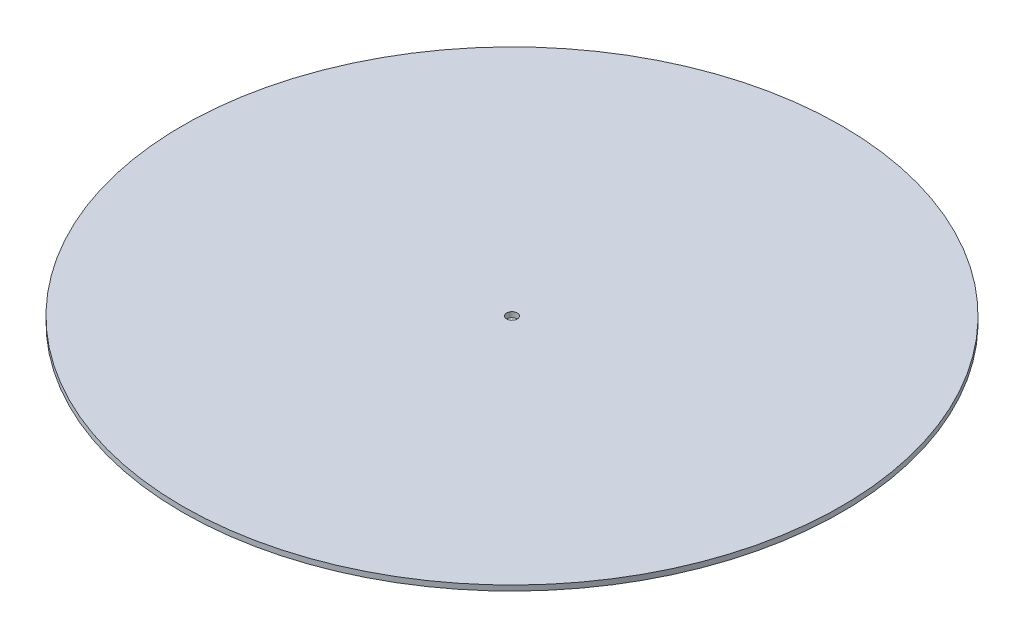
SolidWorks part; units mm, degrees
ref_plane "前视基准面" through (0, 0, 0) normal (0, 0, 1) x (1, 0, 0)
ref_plane "上视基准面" through (0, 0, 0) normal (0, 1, 0) x (1, 0, 0)
ref_plane "右视基准面" through (0, 0, 0) normal (1, 0, 0) x (0, 0, -1)
sketch "草图1" plane through (0, 0, 0) normal (0, 1, 0) x (1, 0, 0)
  circle A0 centre (0, 0) radius 188
extrude "凸台-拉伸1" add sketch "草图1" along normal blind 3
ref_axis "旋转轴" through (0, 3, 0) along (0, -1, 0)
hole_wizard "大小mm 暗销孔1" positions "草图2" profile "草图3" hole size "Ø6.0" standard "ISO" end condition up to next
sketch "草图2" plane through (0, 3, 0) normal (0, 1, 0) x (1, 0, 0)
  point P0 (0, 0)
  point P3 (0, 0)
  point P4 (0, 0)
  point P6 (0, 0)
sketch "草图3" plane through (0, 3, 0) normal (1, 0, 0) x (0, 0, 1)
  line L0 (0, 0) -> (0, 3)
  line L1 (0, 3) -> (3, 3)
  line L2 (3, 3) -> (3, 0)
  line L5 (3, 0) -> (0, 0)
  line L11 (0, -6.35) -> (0, 107.95) construction
  dimension "通孔孔直径" = 6
  dimension "通孔孔深度" = 3
